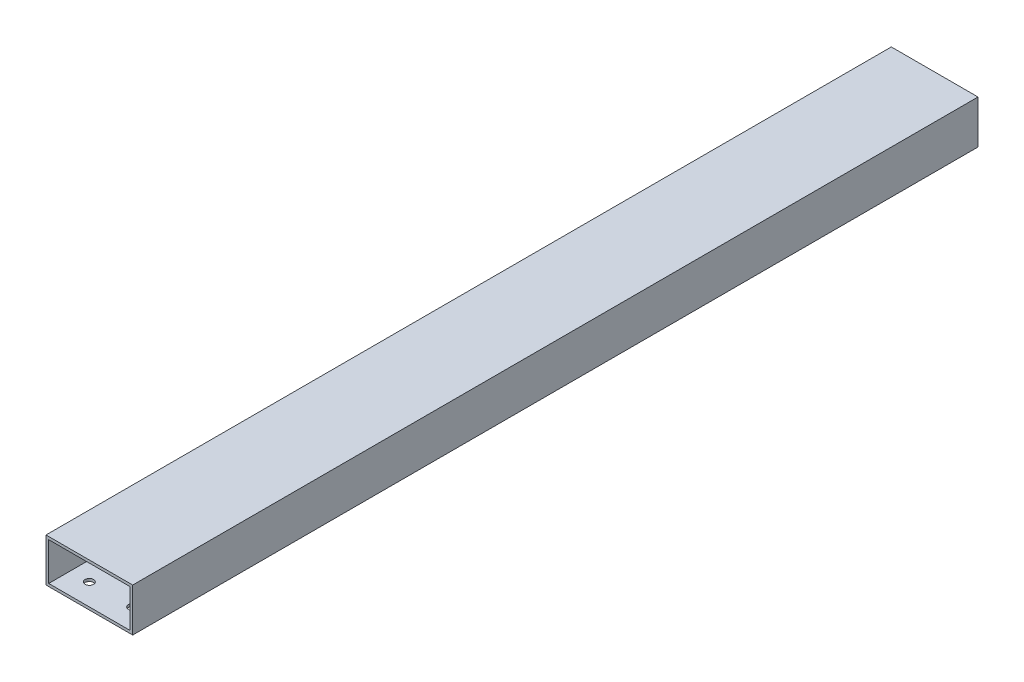
SolidWorks part; units mm, degrees
material "6061-T6 (SS)"
ref_plane "Front Plane" through (0, 0, 0) normal (0, 0, 1) x (1, 0, 0)
ref_plane "Top Plane" through (0, 0, 0) normal (0, 1, 0) x (1, 0, 0)
ref_plane "Right Plane" through (0, 0, 0) normal (1, 0, 0) x (0, 0, -1)
sketch "Sketch1" plane through (0, 0, 0) normal (0, 0, 1) x (1, 0, 0)
  line L1 (-25.4, -12.7) -> (25.4, -12.7)
  line L2 (-25.4, -12.7) -> (-25.4, 12.7)
  line L3 (-25.4, 12.7) -> (25.4, 12.7)
  line L4 (25.4, -12.7) -> (25.4, 12.7)
  line L5 (-25.4, -12.7) -> (25.4, 12.7) construction
  line L6 (-25.4, 12.7) -> (25.4, -12.7) construction
  point P0 (0, 0)
  dimension "D1" = 50.8
  dimension "D2" = 25.4
extrude "Boss-Extrude1" add sketch "Sketch1" along normal blind 495.3 contours L3 L4 L1 L2
shell "Shell1" thickness 1.5875 removed face at (0, 0, 0) removed face at (0, 0, 495.3)
sketch "Sketch2" plane through (0, -12.7, 0) normal (0, 1, 0) x (1, 0, 0)
  line L0 (-25.4, 0) -> (25.4, 0) construction
  circle A0 centre (-12.7, -25.4) radius 2.4892
  circle A1 centre (12.7, -25.4) radius 2.4892
  circle A2 centre (12.7, -50.8) radius 2.4892
  circle A3 centre (12.7, -76.2) radius 2.4892
  circle A4 centre (12.7, -101.6) radius 2.4892
  circle A5 centre (12.7, -127) radius 2.4892
  circle A6 centre (-12.7, -50.8) radius 2.4892
  circle A7 centre (-12.7, -76.2) radius 2.4892
  circle A8 centre (-12.7, -101.6) radius 2.4892
  circle A9 centre (-12.7, -127) radius 2.4892
  dimension "D5" = 4.9784
  dimension "D6" = 12.7
  dimension "D3" = 25.4
  dimension "D4" = 25.4
  dimension "D7" = 25.4
  dimension "D1" = 2
  dimension "D2" = 5
extrude "Cut-Extrude1" cut sketch "Sketch2" along normal up to next
sketch "Sketch3" plane through (0, -12.7, 0) normal (0, -1, 0) x (1, 0, 0)
  line L0 (-25.4, 495.3) -> (-25.4, 0) construction
  line L2 (-25.4, 495.3) -> (25.4, 495.3) construction
  circle A0 centre (-12.7, 457.2) radius 2.4892
  circle A1 centre (12.7, 457.2) radius 2.4892
  circle A2 centre (12.7, 469.9) radius 2.4892
  circle A3 centre (12.7, 482.6) radius 2.4892
  circle A4 centre (-12.7, 469.9) radius 2.4892
  circle A5 centre (-12.7, 482.6) radius 2.4892
  dimension "D1" = 4.9784
  dimension "D4" = 12.7
  dimension "D5" = 12.7
  dimension "D6" = 12.7
  dimension "D7" = 25.4
  dimension "D2" = 2
  dimension "D3" = 3
extrude "Cut-Extrude2" cut sketch "Sketch3" against normal up to next
